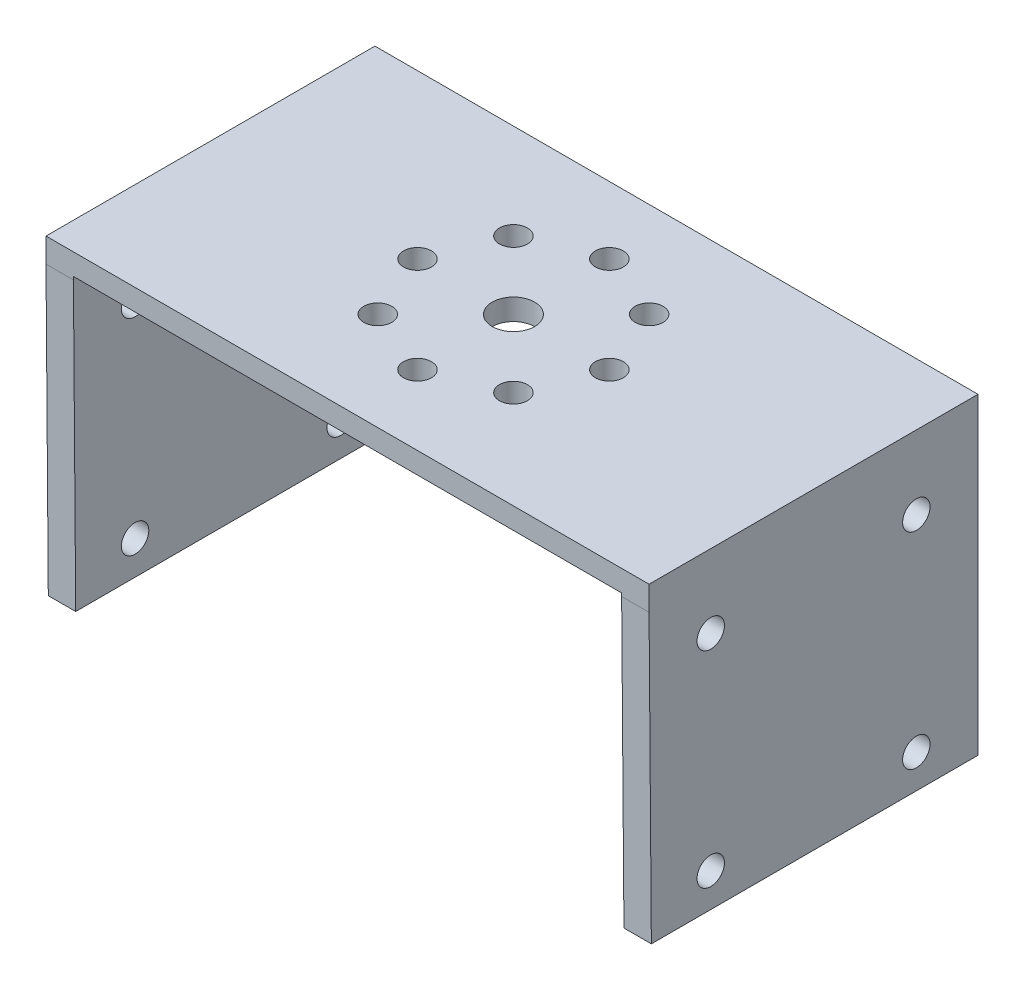
SolidWorks part; units mm, degrees
ref_plane "正面" through (0, 0, 0) normal (0, 0, 1) x (1, 0, 0)
ref_plane "平面" through (0, 0, 0) normal (0, 1, 0) x (1, 0, 0)
ref_plane "右側面" through (0, 0, 0) normal (1, 0, 0) x (0, 0, -1)
sketch "ｽｹｯﾁ1" plane through (0, 0, 0) normal (1, 0, 0) x (0, 0, -1)
  line L1 (-6.5181, 29.2479) -> (-26.5181, 29.2479)
  line L2 (-6.5181, 29.2479) -> (-6.5181, -10.7521)
  line L3 (-6.5181, -10.7521) -> (-26.5181, -10.7521)
  line L4 (-26.5181, 29.2479) -> (-26.5181, -10.7521)
extrude "ﾎﾞｽ - 押し出し1" add sketch "ｽｹｯﾁ1" along normal blind 40
sketch "ｽｹｯﾁ2" plane through (0, 0, 0) normal (-1, 0, 0) x (0, 0, 1)
  line L6 (26.5181, -10.7521) -> (6.5181, -10.7521) construction
  line L7 (16.5181, -10.7521) -> (16.5181, -0.7521)
  circle A0 centre (9.0181, 26.2015) radius 1
  circle A1 centre (9.0181, 11.2015) radius 1
  circle A2 centre (24.0181, 11.2015) radius 1
  circle A3 centre (24.0181, 26.2015) radius 1
extrude "ｶｯﾄ - 押し出し3" cut sketch "ｽｹｯﾁ2" against normal blind 40 contours A0 | A1 | A2 | A3 region at (0, 26.2015, 9.0181) region at (0, 11.2015, 9.0181) region at (0, 11.2015, 24.0181)
ref_plane "平面1" through (0, 0, 0) normal (-1, 0, 0) x (0, 0, 1)
sketch "ｽｹｯﾁ4" plane through (0, 0, 0) normal (-1, 0, 0) x (0, 0, 1)
  line L0 (6.5181, -10.7521) -> (26.5181, 29.2479)
  line L1 (6.5181, 29.2479) -> (26.5181, -10.7521)
  line L3 (26.5181, -10.7521) -> (6.5181, -10.7521) construction
  line L4 (16.5181, -10.7521) -> (16.5181, -0.7521)
  circle A0 centre (16.5181, -0.7521) radius 1.5
extrude "ﾎﾞｽ - 押し出し2" add sketch "ｽｹｯﾁ4" along normal blind 5 and the other way blind 45 contours A0 region at (0, -1.7827, 17.5488)
chamfer "面取り1" distance 2 angle 45 4 edges at (20, 29.2479, 26.5181) (20, 29.2479, 6.5181) (20, -10.7521, 6.5181) (20, -10.7521, 26.5181)
fillet "ﾌｨﾚｯﾄ1" radius 1 16 edges at (0, 28.2479, 25.5181) (0, 29.2479, 16.5181) (0, 28.2479, 7.5181) (0, 9.2479, 6.5181) (0, -9.7521, 7.5181) (0, -10.7521, 16.5181) (0, -9.7521, 25.5181) (0, 9.2479, 26.5181) (40, -9.7521, 7.5181) (40, -10.7521, 16.5181) (40, -9.7521, 25.5181) (40, 9.2479, 26.5181) (40, 28.2479, 25.5181) (40, 29.2479, 16.5181) (40, 28.2479, 7.5181) (40, 9.2479, 6.5181)
sketch "ｽｹｯﾁ5" plane through (-5, 0, 0) normal (-1, 0, 0) x (0, 0, 1)
  circle A0 centre (16.5181, -0.7521) radius 3
extrude "ﾎﾞｽ - 押し出し3" add sketch "ｽｹｯﾁ5" against normal blind 50
ref_plane "平面2" through (-5, 0, 0) normal (-1, 0, 0) x (0, 0, 1)
sketch "ｽｹｯﾁ7" plane through (-5, 0, 0) normal (-1, 0, 0) x (0, 0, 1)
  circle A0 centre (16.5181, -0.7521) radius 3
extrude "ﾎﾞｽ - 押し出し4" add sketch "ｽｹｯﾁ7" along normal blind 1.5 and the other way blind 53
sketch "ｽｹｯﾁ12" plane through (0, 0, 0) normal (0, 0, 1) x (1, 0, 0)
  line L0 (48, -3.7521) -> (48, 2.2479) construction
  line L1 (48, 3.104) -> (46.5, 3.104)
  line L2 (48, 3.104) -> (48, -3.7521)
  line L3 (48, -3.7521) -> (46.5, -3.7521)
  line L4 (46.5, 3.104) -> (46.5, -3.7521)
  line L5 (40, -3.7521) -> (48, -3.7521) construction
  dimension "D1" = 1.5
extrude "ｶｯﾄ - 押し出し6" cut sketch "ｽｹｯﾁ12" along normal blind 25.5
ref_plane "平面3" through (-6.5, 0, 0) normal (-1, 0, 0) x (0, 0, 1)
ref_plane "平面4" through (0, 0, 0) normal (-1, 0, 0) x (0, 0, 1)
sketch "ｽｹｯﾁ9" plane through (0, 0, 0) normal (-1, 0, 0) x (0, 0, 1)
  circle A0 centre (16.5181, -0.7521) radius 3
extrude "ﾎﾞｽ - 押し出し7" add sketch "ｽｹｯﾁ9" along normal blind 6.5
sketch "ｽｹｯﾁ13" plane through (0, 0, 0) normal (-1, 0, 0) x (0, 0, 1)
  line L0 (26.5181, 8.7432) -> (26.5181, 29.7769)
  line L1 (26.5181, 27.2479) -> (26.5181, -8.7521) construction
  line L2 (26.5181, 29.7769) -> (6.5181, 29.7769)
  line L3 (26.5181, 8.7432) -> (6.5181, 8.7432)
  line L4 (6.5181, -8.7521) -> (6.5181, 27.2479) construction
  line L5 (6.5181, 8.7432) -> (6.5181, 29.7769)
  line L6 (6.5181, 29.7769) -> (4.5181, 29.7769)
  line L7 (26.5181, 29.7769) -> (28.5181, 29.7769)
  line L8 (4.5181, 29.7769) -> (4.5181, 8.7432)
  line L9 (4.5181, 8.7432) -> (6.5181, 8.7432)
  line L10 (28.5181, 29.7769) -> (28.3506, 8.7432)
  line L11 (28.3506, 8.7432) -> (26.5181, 8.7432)
  line L13 (4.5181, 29.7769) -> (28.5181, 29.7769)
  line L14 (4.5181, 29.7769) -> (4.5181, 31.5544)
  line L15 (4.5181, 31.5544) -> (28.5181, 31.5544)
  line L16 (28.5181, 29.7769) -> (28.5181, 31.5544)
  circle A0 centre (24.0181, 26.2015) radius 1
  circle A1 centre (9.0181, 26.2015) radius 1
  circle A2 centre (9.0181, 11.2015) radius 1
  circle A3 centre (24.0181, 11.2015) radius 1
  line M5 (25.5181, -8.3379) -> (25.5181, 26.8337)
  line M6 (25.5181, 26.8337) -> (24.1039, 28.2479)
  line M7 (24.1039, 28.2479) -> (8.9323, 28.2479)
  line M8 (8.9323, 28.2479) -> (7.5181, 26.8337)
  line M9 (7.5181, 26.8337) -> (7.5181, -8.3379)
  circle M13 centre (24.0181, 11.2015) radius 1
  circle M14 centre (9.0181, 11.2015) radius 1
  circle M15 centre (9.0181, 26.2015) radius 1
  circle M16 centre (24.0181, 26.2015) radius 1
extrude "ﾎﾞｽ - 押し出し9" add sketch "ｽｹｯﾁ13" against normal blind 42 and the other way blind 2 contours L3 M5 M6 M7 M8 M9 M14 M16 M15 M13 | L8 L9 L5 L6 | L5 L3 L0 L2 M9 M8 M7 M6 M5 | L7 L16 L15 L14 L6 L2 | L11 L10 L7 L0 region at (0, 9.0334, 26.0181) region at (0, 19.4132, 27.4768) region at (0, 30.6657, 16.5181) region at (0, 18.4327, 16.5181) region at (0, 19.26, 5.5181)
sketch "ｽｹｯﾁ14" plane through (0, 0, 6.5181) normal (0, 0, -1) x (-1, 0, 0)
  line L0 (-40, 2.4268) -> (-40, 30.0018)
  line L1 (-40, -8.3379) -> (-40, 8.7432) construction
  line L2 (-40, 30.0018) -> (0, 30.0018)
  line L3 (0, -9.9) -> (0, 9.9) construction
  line L4 (0, 30.0018) -> (0, 7.074)
  line L5 (0, 7.074) -> (16.8252, 7.4286)
  line L6 (16.8252, 7.4286) -> (20.4298, -19.9901)
  line L7 (20.4298, -19.9901) -> (-71.1038, -17.1537)
  line L8 (-71.1038, -17.1537) -> (-61.1763, 0)
  line L9 (-61.1763, 0) -> (-52.0171, 5.8922)
  line L10 (-52.0171, 5.8922) -> (-40, 2.4268)
extrude "ｶｯﾄ - 押し出し8" cut sketch "ｽｹｯﾁ14" against normal blind 42 and the other way blind 42
sketch "ｽｹｯﾁ15" plane through (0, 30.0018, 0) normal (0, -1, 0) x (1, 0, 0)
  circle A0 centre (20, 16.4134) radius 1.548
  circle A1 centre (20, 23.4134) radius 1.02
  circle A2 centre (15.0503, 21.3631) radius 1.02
  circle A3 centre (13, 16.4134) radius 1.02
  circle A4 centre (15.0503, 11.4636) radius 1.02
  circle A5 centre (20, 9.4134) radius 1.02
  circle A6 centre (24.9497, 11.4636) radius 1.02
  circle A7 centre (27, 16.4134) radius 1.02
  circle A8 centre (24.9497, 21.3631) radius 1.02
extrude "ｶｯﾄ - 押し出し9" cut sketch "ｽｹｯﾁ15" against normal blind 42
